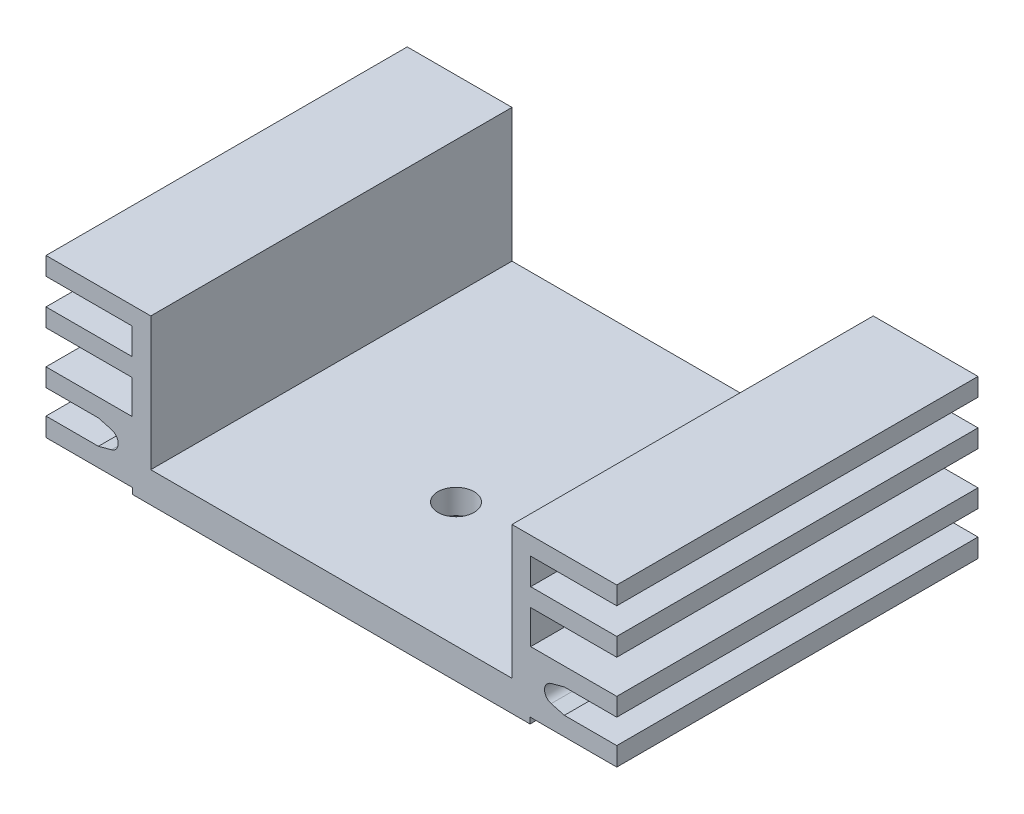
SolidWorks part; units mm, degrees
ref_plane "Front Plane" through (0, 0, 0) normal (0, 0, 1) x (1, 0, 0)
ref_plane "Top Plane" through (0, 0, 0) normal (0, 1, 0) x (1, 0, 0)
ref_plane "Right Plane" through (0, 0, 0) normal (1, 0, 0) x (0, 0, -1)
sketch "Sketch1" plane through (0, 0, 0) normal (0, 0, 1) x (1, 0, 0)
  line L0 (0, 24.3033) -> (0, -14.3062) construction
  line L1 (-15, 13.1) -> (-15, 2.04)
  line L2 (-15, 2.04) -> (15, 2.04)
  line L3 (-15, 13.1) -> (-23.7, 13.1)
  line L4 (-23.7, 13.1) -> (-23.7, 11.6)
  line L5 (-23.7, 11.6) -> (-16.55, 11.6)
  line L6 (16.5, -0.5) -> (-16.5, -0.5)
  line L7 (-16.5, -0.5) -> (-16.5, 0)
  line L8 (-16.5, 0) -> (-23.7, 0)
  line L9 (-23.7, 0) -> (-23.7, 1.55)
  line L10 (-23.7, 9.4) -> (-23.7, 7.9)
  line L11 (-23.7, 7.9) -> (-16.55, 7.9)
  line L12 (-23.7, 9.4) -> (-16.55, 9.4)
  line L13 (-16.55, 9.4) -> (-16.55, 11.6)
  line L14 (-23.7, 1.55) -> (-19.35, 1.55)
  line L15 (-19.35, 1.55) -> (-18.2544, 1.846)
  line L16 (-19.35, 3.59) -> (-23.7, 3.59)
  line L17 (-16.55, 7.9) -> (-16.55, 5.09)
  line L18 (-16.55, 5.09) -> (-23.7, 5.09)
  line L19 (-23.7, 5.09) -> (-23.7, 3.59)
  line L20 (-18.2544, 3.294) -> (-19.35, 3.59)
  line L21 (-23.7, 3.59) -> (-23.7, 1.55) construction
  line L22 (-23.7, 2.57) -> (-16.1511, 2.57) construction
  line L23 (23.7, 2.57) -> (16.1511, 2.57) construction
  line L24 (23.7, 3.59) -> (23.7, 1.55) construction
  line L25 (18.2544, 3.294) -> (19.35, 3.59)
  line L26 (23.7, 5.09) -> (23.7, 3.59)
  line L27 (16.55, 5.09) -> (23.7, 5.09)
  line L28 (16.55, 7.9) -> (16.55, 5.09)
  line L29 (19.35, 3.59) -> (23.7, 3.59)
  line L30 (19.35, 1.55) -> (18.2544, 1.846)
  line L31 (23.7, 1.55) -> (19.35, 1.55)
  line L32 (16.55, 9.4) -> (16.55, 11.6)
  line L33 (23.7, 9.4) -> (16.55, 9.4)
  line L34 (23.7, 7.9) -> (16.55, 7.9)
  line L35 (23.7, 9.4) -> (23.7, 7.9)
  line L36 (23.7, 0) -> (23.7, 1.55)
  line L37 (16.5, 0) -> (23.7, 0)
  line L38 (16.5, -0.5) -> (16.5, 0)
  line L39 (23.7, 11.6) -> (16.55, 11.6)
  line L40 (23.7, 13.1) -> (23.7, 11.6)
  line L41 (15, 13.1) -> (23.7, 13.1)
  line L42 (15, 13.1) -> (15, 2.04)
  arc A0 (-18.2544, 1.846) -> (-18.2544, 3.294) centre (-18.45, 2.57) ccw
  arc A1 (18.2544, 1.846) -> (18.2544, 3.294) centre (18.45, 2.57) cw
  point P47 (0, -0.5)
  point P51 (0, 2.04)
  dimension "D12" = 4.35
  dimension "D13" = 0.75
  dimension "D1" = 47.4
  dimension "D2" = 30
  dimension "D3" = 13.1
  dimension "D4" = 1.5
  dimension "D5" = 7.15
  dimension "D7" = 2.2
  dimension "D8" = 2.54
  dimension "D9" = 0.5
  dimension "D10" = 33
  dimension "D11" = 1.55
  dimension "D14" = 2.04
  dimension "D15" = 5.25
  dimension "D6" = 2
extrude "Boss-Extrude1" add sketch "Sketch1" along normal mid plane 30
sketch "Sketch2" plane through (0, -0.5, 0) normal (0, -1, 0) x (1, 0, 0)
  line L0 (-16.5, 15) -> (16.5, 15) construction
  circle A0 centre (0, 4.65) radius 1.5
  point P5 (0, 0)
  dimension "D1" = 10.35
  dimension "D2" = 3
extrude "Cut-Extrude1" cut sketch "Sketch2" against normal through all
chamfer "Chamfer1" distance 0.5 angle 45 1 edges at (0, -0.5, 3.15)
